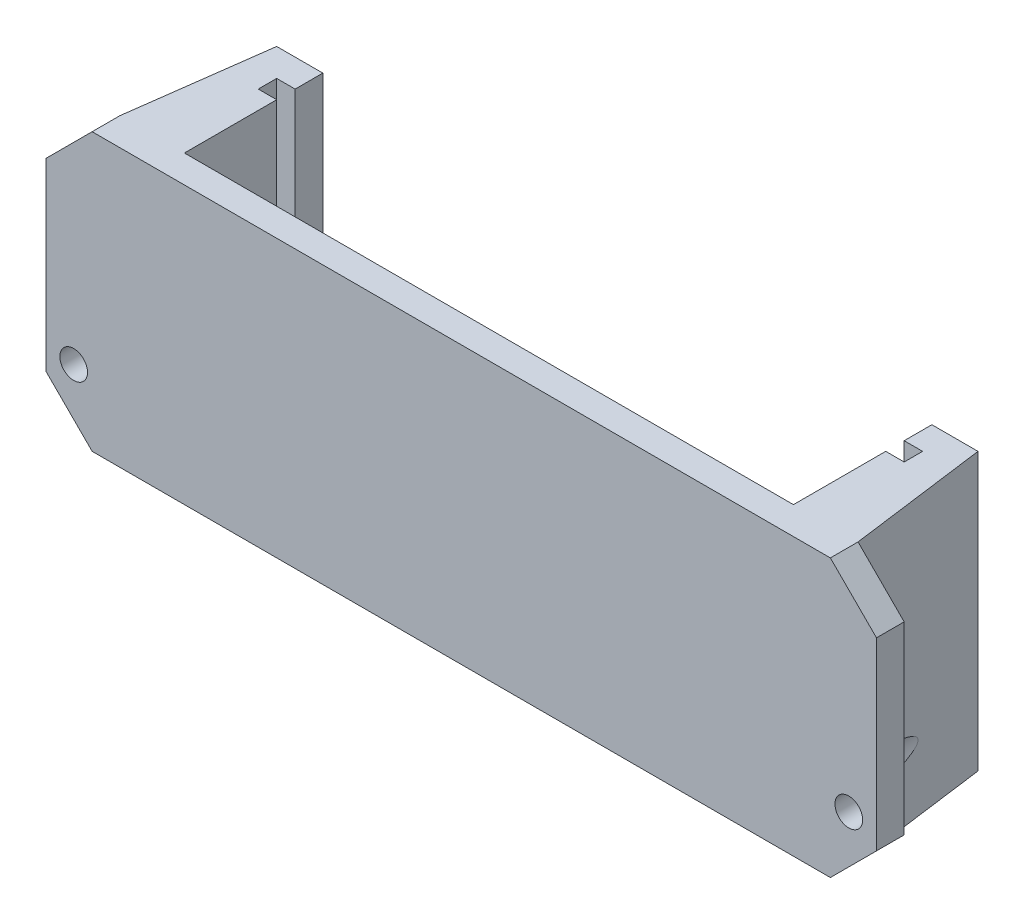
SolidWorks part; units mm, degrees
ref_plane "Front Plane" through (0, 0, 0) normal (0, 0, 1) x (1, 0, 0)
ref_plane "Top Plane" through (0, 0, 0) normal (0, 1, 0) x (1, 0, 0)
ref_plane "Right Plane" through (0, 0, 0) normal (1, 0, 0) x (0, 0, -1)
sketch "Sketch1" plane through (0, 0, 0) normal (0, 1, 0) x (1, 0, 0)
  line L0 (2, -3.1072) -> (2, 6.8928)
  line L1 (-10, -3.1072) -> (80, -3.1072)
  line L2 (-10, -3.1072) -> (-10, -6.1072)
  line L3 (-10, -6.1072) -> (80, -6.1072)
  line L4 (80, -3.1072) -> (80, -6.1072)
  line L5 (2, 6.8928) -> (0, 6.8928)
  line L6 (0, 6.8928) -> (0, 8.8928)
  line L7 (0, 8.8928) -> (2, 8.8928)
  line L8 (2, 8.8928) -> (2, 11.8928)
  line L9 (2, 11.8928) -> (-3, 11.8928)
  line L10 (-3, 11.8928) -> (-5, -3.1072)
  line L11 (68, -3.1072) -> (68, 6.8928)
  line L12 (68, 6.8928) -> (70, 6.8928)
  line L13 (70, 6.8928) -> (70, 8.8928)
  line L14 (70, 8.8928) -> (68, 8.8928)
  line L15 (68, 8.8928) -> (68, 11.8928)
  line L16 (68, 11.8928) -> (73, 11.8928)
  line L17 (73, 11.8928) -> (75, -3.1072)
  point P15 (0, 0)
  dimension "D1" = 3
  dimension "D2" = 90
  dimension "D3" = 2
  dimension "D4" = 2
  dimension "D5" = 10
  dimension "D6" = 3
  dimension "D7" = 7
  dimension "D8" = 70
  dimension "D9" = 5
  dimension "D10" = 12
extrude "Boss-Extrude1" add sketch "Sketch1" along normal blind 30 contours L4 L1 L2 L3 | L9 L10 L1 L0 L5 L6 L7 L8 | L17 L16 L15 L14 L13 L12 L11 L1 region at (-1.1221, 0, -3.794) region at (35, 0, 4.6072) region at (71.1221, 0, -3.794)
sketch "Sketch2" plane through (0, 0, 3.1072) normal (0, 0, -1) x (-1, 0, 0)
  line L0 (10, 30) -> (10, 0) construction
  circle A0 centre (7, 7.1547) radius 1.5
  circle A1 centre (-77, 7.1547) radius 1.5
  circle A2 centre (7, 7.1547) radius 3
  circle A3 centre (-77, 7.1547) radius 3
  dimension "D1" = 84
  dimension "D3" = 3
  dimension "D4" = 6
  dimension "D2" = 3
extrude "Cut-Extrude1" cut sketch "Sketch2" against normal blind 20 contours A0 | A1 region at (-7, 7.1547, 3.1072) region at (77, 7.1547, 3.1072)
extrude "Cut-Extrude2" cut sketch "Sketch2<3>" along normal blind 20
sketch "Sketch2<3>" plane through (0, 0, 3.1072) normal (0, 0, -1) x (-1, 0, 0) same geometry as "Sketch2"
chamfer "Chamfer1" distance 5 angle 45 4 edges at (80, 0, 4.6072) (80, 30, 4.6072) (-10, 0, 4.6072) (-10, 30, 4.6072)
